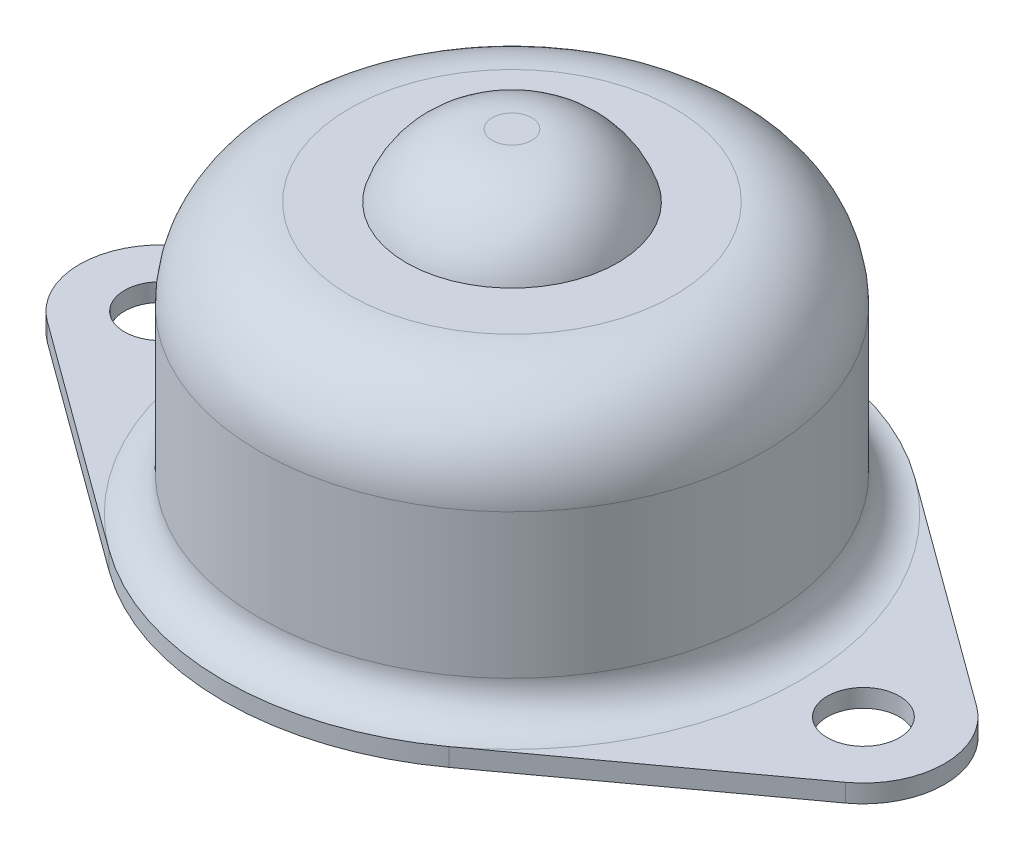
SolidWorks part; units mm, degrees
ref_plane "Спереди" through (0, 0, 0) normal (0, 0, 1) x (1, 0, 0)
ref_plane "Сверху" through (0, 0, 0) normal (0, 1, 0) x (1, 0, 0)
ref_plane "Справа" through (0, 0, 0) normal (1, 0, 0) x (0, 0, -1)
sketch "Sketch1" plane through (0, 0, 0) normal (0, 1, 0) x (1, 0, 0)
  line L0 (0, 0) -> (19.5, 0) construction
  line L1 (0, 0) -> (0, 16) construction
  line L2 (0, 0) -> (-19.5, 0) construction
  line L3 (-22.1538, 3.6342) -> (-9.4359, 12.9214)
  line L4 (22.1538, 3.6342) -> (9.4359, 12.9214)
  line L5 (-22.1538, -3.6342) -> (-9.4359, -12.9214)
  line L6 (22.1538, -3.6342) -> (9.4359, -12.9214)
  line L7 (-24, 0) -> (-24, -15.745) construction
  line L8 (24, 0) -> (24, -15.745) construction
  arc A0 (-9.4359, -12.9214) -> (9.4359, -12.9214) centre (0, 0) ccw
  circle A1 centre (19.5, 0) radius 2
  circle A2 centre (-19.5, 0) radius 2
  arc A3 (-22.1538, 3.6342) -> (-22.1538, -3.6342) centre (-19.5, 0) ccw
  arc A4 (22.1538, -3.6342) -> (22.1538, 3.6342) centre (19.5, 0) ccw
  arc A5 (9.4359, 12.9214) -> (-9.4359, 12.9214) centre (0, 0) ccw
  dimension "D1" = 32
  dimension "D2" = 4
  dimension "D3" = 48
  dimension "D4" = 2.5
extrude "Boss-Extrude1" add sketch "Sketch1" along normal blind 1
sketch "Sketch2" plane through (0, 1, 0) normal (0, 1, 0) x (1, 0, 0)
  circle A0 centre (0, 0) radius 14
  dimension "D1" = 28
extrude "Boss-Extrude2" add sketch "Sketch2" along normal blind 15
fillet "Fillet1" radius 5 1 edges at (0, 16, 14)
sketch "Sketch3" plane through (0, 16, 0) normal (0, 1, 0) x (1, 0, 0)
  circle A0 centre (0, 0) radius 5.8635
extrude "Boss-Extrude3" add sketch "Sketch3" along normal blind 3.5
fillet "Fillet2" radius 5 1 edges at (0, 19.5, 5.8635)
fillet "Fillet3" radius 2 1 edges at (0, 1, 14)
